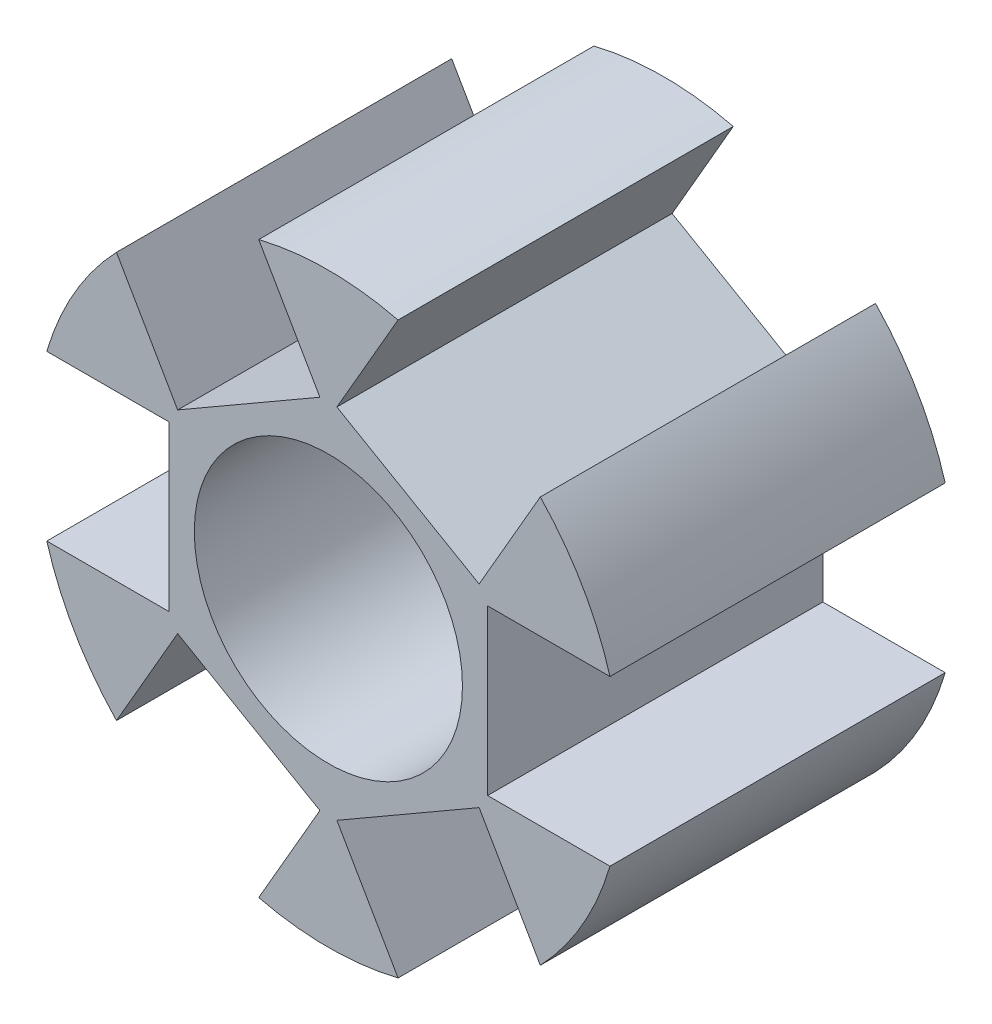
SolidWorks part; units mm, degrees
ref_plane "Top Plane" through (0, 0, 0) normal (0, 0, 1) x (1, 0, 0)
ref_plane "Right Plane" through (0, 0, 0) normal (0, 1, 0) x (1, 0, 0)
ref_plane "Front Plane" through (0, 0, 0) normal (1, 0, 0) x (0, 0, -1)
ref_axis "x-axis" through (-88.99, 0, 0) along (1, 0, 0)
ref_axis "y-axis" through (0, -55, 0) along (0, 1, 0)
ref_axis "z-axis" through (0, 0, 55) along (0, 0, -1)
sketch "Sketch1" plane through (0, 0, 0) normal (0, 0, 1) x (1, 0, 0)
  line L8 (-19.9785, 0) -> (0, 0) construction
  line L16 (0, 0) -> (0, -20.7846) construction
  line L23 (0, 0) -> (0, -20.7846) construction
  circle A0 centre (0, 0) radius 4
  circle A3 centre (0, 0) radius 8.75
  dimension "D1" = 8
  dimension "D2" = 17.5
extrude "Boss-Extrude1" add sketch "Sketch1" along normal mid plane 10
ref_plane "Plane1" through (-8.75, 0, 0) normal (-1, 0, 0) x (0, 0, 1)
sketch "Sketch2" plane through (-8.75, -17.1931, 0) normal (1, 0, 0) x (0, -1, 0)
  line L1 (-19.6431, -5) -> (-14.7431, -5)
  line L2 (-19.6431, -5) -> (-19.6431, 5)
  line L3 (-19.6431, 5) -> (-14.7431, 5)
  line L4 (-14.7431, -5) -> (-14.7431, 5)
  line L5 (-19.6431, -5) -> (-14.7431, 5) construction
  line L6 (-19.6431, 5) -> (-14.7431, -5) construction
  point P0 (-17.1931, 0)
  dimension "D1" = 4.9
  dimension "D2" = 10
extrude "Cut-Extrude3" cut sketch "Sketch2" along normal blind 4
pattern_circular "CirPattern1" count 6 over 360 about axis through (0, 0, 5) along (0, 0, 1) of "Cut-Extrude3"
